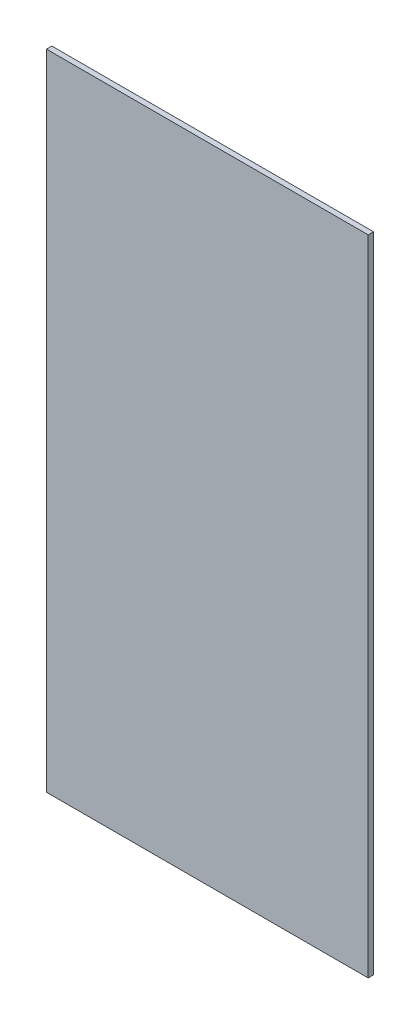
SolidWorks part; units mm, degrees
ref_plane "Front Plane" through (0, 0, 0) normal (0, 0, 1) x (1, 0, 0)
ref_plane "Top Plane" through (0, 0, 0) normal (0, 1, 0) x (1, 0, 0)
ref_plane "Right Plane" through (0, 0, 0) normal (1, 0, 0) x (0, 0, -1)
sketch "Sketch2" plane through (0, 0, 0) normal (0, 0, 1) x (1, 0, 0)
  line L1 (0, 0) -> (190.5, 0)
  line L2 (0, 0) -> (0, 381)
  line L3 (0, 381) -> (190.5, 381)
  line L4 (190.5, 0) -> (190.5, 381)
  dimension "D1" = 190.5
  dimension "D2" = 381
extrude "Boss-Extrude1" add sketch "Sketch2" along normal blind 3.175
